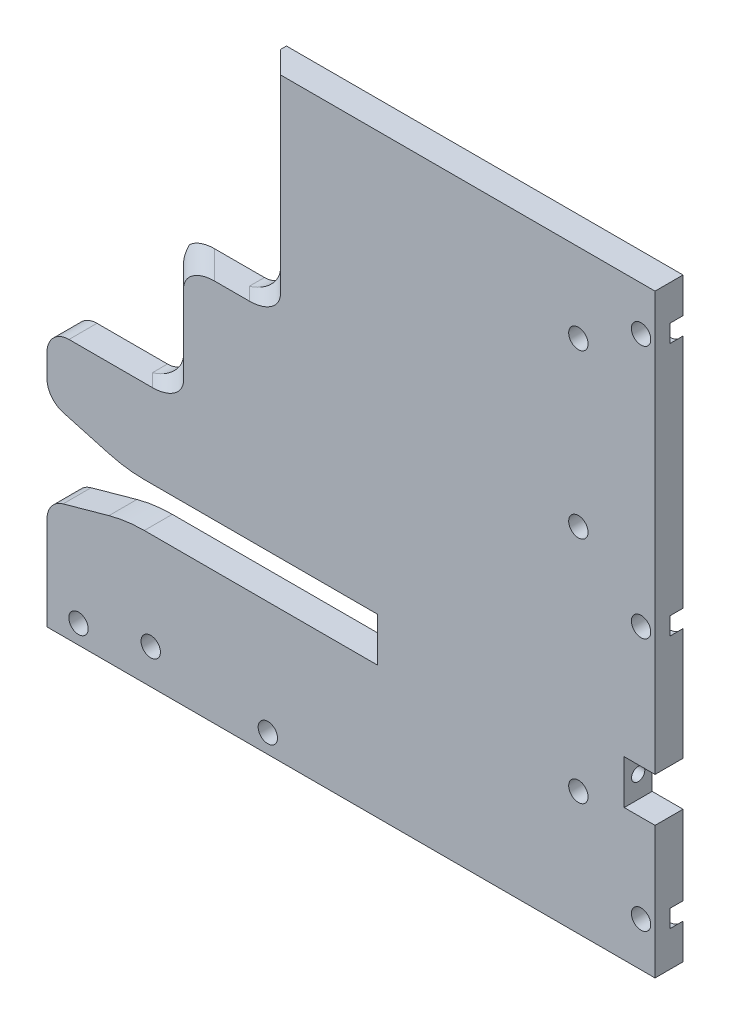
SolidWorks part; units mm, degrees
material "1060 Alloy"
ref_plane "Front Plane" through (0, 0, 0) normal (0, 0, 1) x (1, 0, 0)
ref_plane "Top Plane" through (0, 0, 0) normal (0, 1, 0) x (1, 0, 0)
ref_plane "Right Plane" through (0, 0, 0) normal (1, 0, 0) x (0, 0, -1)
sketch "Sketch1" plane through (0, 0, 0) normal (0, 0, 1) x (1, 0, 0)
  line L0 (0, 0) -> (-138, 0)
  line L1 (-138, 0) -> (-138, 30)
  line L2 (-138, 30) -> (-63, 30)
  line L3 (-63, 30) -> (-63, 40)
  line L4 (-63, 40) -> (-138, 40)
  line L5 (-138, 40) -> (-138, 59)
  line L6 (-138, 59) -> (-112, 59)
  line L7 (-112, 59) -> (-112, 87)
  line L8 (-112, 87) -> (-90, 87)
  line L9 (-90, 87) -> (-90, 135)
  line L10 (-90, 135) -> (0, 135)
  line L11 (0, 135) -> (0, 0)
  point P10 (-120, 40)
  point P14 (-120, 30)
  dimension "D1" = 30
  dimension "D2" = 138
  dimension "D3" = 75
  dimension "D4" = 10
  dimension "D5" = 19
  dimension "D6" = 26
  dimension "D7" = 28
  dimension "D8" = 135
  dimension "D9" = 22
  dimension "D10" = 18
extrude "Boss-Extrude1" add sketch "Sketch1" along normal blind 6.35
sketch "Sketch4" plane through (0, 0, 0) normal (0, 0, -1) x (-1, 0, 0)
  line L0 (120, 40) -> (138, 45)
  line L1 (138, 40) -> (138, 59) construction
  line L2 (138, 45) -> (138, 40)
  line L3 (138, 40) -> (120, 40)
  line L4 (120, 30) -> (138, 30)
  line L5 (138, 30) -> (138, 25)
  line L6 (138, 0) -> (138, 30) construction
  line L7 (138, 25) -> (120, 30)
  dimension "D1" = 5
  dimension "D2" = 5
extrude "Cut-Extrude1" cut sketch "Sketch4" against normal through all
sketch "Sketch5" plane through (-63, 0, 0) normal (-1, 0, 0) x (0, 0, 1)
  line L0 (6.35, 30) -> (0, 30) construction
  circle A0 centre (3.175, 35) radius 1.5
  point P5 (3.175, 30)
  dimension "D1" = 3
extrude "Cut-Extrude2" cut sketch "Sketch5" against normal through all
fillet "Fillet1" radius 30 2 edges at (-120, 40, 3.175) (-120, 30, 3.175)
chamfer "Chamfer1" distance 5 angle 45 2 edges at (-112, 73, 6.35) (-90, 111, 6.35)
fillet "Fillet2" radius 5 3 edges at (-138, 25, 3.175) (-138, 45, 3.175) (-138, 59, 3.175)
fillet "Fillet3" radius 5 4 edges at (-87.5, 87, 3.85) (-90, 87, 0.675) (-109.5, 59, 3.85) (-112, 59, 0.675)
sketch "Sketch6" plane through (0, 0, 0) normal (0, 0, -1) x (-1, 0, 0)
  line L0 (0, 0) -> (0, 135) construction
  line L1 (0, 40) -> (7, 40)
  line L2 (0, 40) -> (0, 30)
  line L3 (0, 30) -> (7, 30)
  line L4 (7, 40) -> (7, 30)
  line L5 (115.9107, 40) -> (63, 40) construction
  line L6 (63, 30) -> (115.9107, 30) construction
  dimension "D1" = 7
extrude "Cut-Extrude3" cut sketch "Sketch6" against normal through all
sketch "Sketch8" plane through (0, 0, 0) normal (0, 0, -1) x (-1, 0, 0)
  line L0 (0, 40) -> (0, 135) construction
  line L1 (0, 135) -> (90, 135) construction
  line L2 (138, 0) -> (0, 0) construction
  point P0 (3.175, 125)
  point P1 (3.175, 67.5)
  point P2 (3.175, 10)
  dimension "D1" = 3.175
  dimension "D2" = 10
  dimension "D3" = 10
  dimension "D4" = 67.5
hole_wizard "Hole1" positions "Sketch9" profile "Sketch10" legacy end condition through all
sketch "Sketch9" plane through (0, 0, 0) normal (0, 0, -1) x (-1, 0, 0)
  point P0 (3.175, 125)
  point P3 (3.175, 67.5)
  point P6 (3.175, 10)
sketch "Sketch10" plane through (-3.175, 125, 0) normal (1, 0, 0) x (0, 1, 0)
  line L0 (0, 0) -> (0, 6.35)
  line L1 (0, 6.35) -> (2.2, 6.35)
  line L2 (2.2, 6.35) -> (2.2, 3)
  line L3 (2.2, 3) -> (3.75, 3)
  line L4 (3.75, 3) -> (3.75, 0)
  line L5 (3.75, 0) -> (0, 0)
  line L6 (0, 110) -> (0, -10) construction
  dimension "Diameter" = 4.4
  dimension "Depth" = 6.35
  dimension "C-Bore Diameter" = 7.5
  dimension "C-Bore Depth" = 3
sketch "Sketch11" plane through (0, 0, 0) normal (0, 0, -1) x (-1, 0, 0)
  point P0 (17.4, 117)
  point P1 (17.4, 80)
  point P3 (17.4, 28)
hole_wizard "Hole2" positions "Sketch12" profile "Sketch13" legacy end condition through all
sketch "Sketch12" plane through (0, 0, 0) normal (0, 0, -1) x (-1, 0, 0)
  point P0 (17.4, 117)
  point P3 (17.4, 80)
  point P6 (17.4, 28)
sketch "Sketch13" plane through (-17.4, 117, 0) normal (1, 0, 0) x (0, 1, 0)
  line L0 (0, 0) -> (0, 6.35)
  line L1 (0, 6.35) -> (2.2, 6.35)
  line L2 (2.2, 6.35) -> (2.2, 3)
  line L3 (2.2, 3) -> (3.75, 3)
  line L4 (3.75, 3) -> (3.75, 0)
  line L5 (3.75, 0) -> (0, 0)
  line L6 (0, 110) -> (0, -10) construction
  dimension "Diameter" = 4.4
  dimension "Depth" = 6.35
  dimension "C-Bore Diameter" = 7.5
  dimension "C-Bore Depth" = 3
fillet "Fillet4" radius 5 1 edges at (-109.5, 87, 3.85)
hole_wizard "Hole3" positions "Sketch14" profile "Sketch15" legacy end condition through all
sketch "Sketch14" plane through (0, 0, 0) normal (0, 0, -1) x (-1, 0, 0)
  point P0 (87.8704, 4.2936)
  point P3 (114.4514, 7.9069)
  point P6 (130.845, 4.2936)
sketch "Sketch15" plane through (-87.8704, 4.2936, 0) normal (1, 0, 0) x (0, 1, 0)
  line L0 (0, 0) -> (0, 6.35)
  line L1 (0, 6.35) -> (2.2, 6.35)
  line L2 (2.2, 6.35) -> (2.2, 3)
  line L3 (2.2, 3) -> (3.75, 3)
  line L4 (3.75, 3) -> (3.75, 0)
  line L5 (3.75, 0) -> (0, 0)
  line L6 (0, 110) -> (0, -10) construction
  dimension "Diameter" = 4.4
  dimension "Depth" = 6.35
  dimension "C-Bore Diameter" = 7.5
  dimension "C-Bore Depth" = 3
